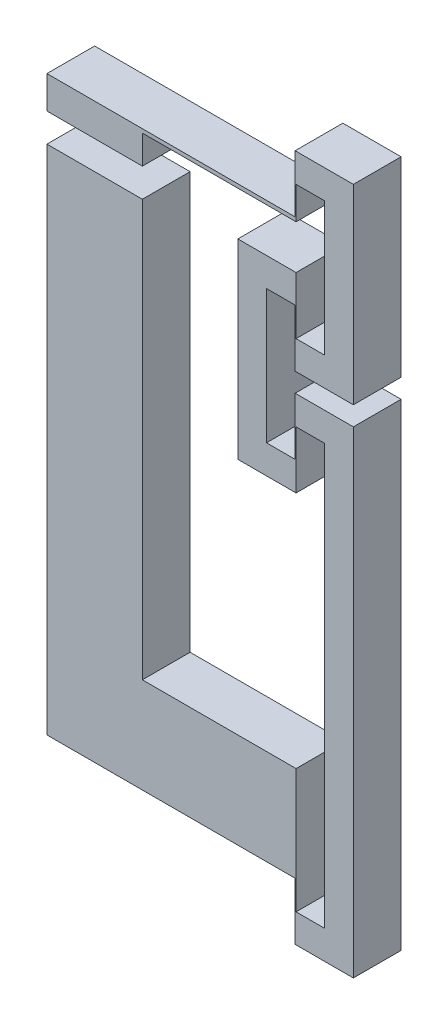
SolidWorks part; units mm, degrees
ref_plane "Front Plane" through (0, 0, 0) normal (0, 0, 1) x (1, 0, 0)
ref_plane "Top Plane" through (0, 0, 0) normal (0, 1, 0) x (1, 0, 0)
ref_plane "Right Plane" through (0, 0, 0) normal (1, 0, 0) x (0, 0, -1)
sketch "Sketch1" plane through (0, 0, 0) normal (0, 0, 1) x (1, 0, 0)
  line L0 (0, 0) -> (0, 53.6)
  line L4 (10, 10) -> (10, 53.6)
  line L5 (10, 53.6) -> (0, 53.6)
  line L6 (0, 56.6) -> (0, 60)
  line L7 (0, 60) -> (26, 60)
  line L8 (26.1, 60) -> (26.1, 59.6)
  line L9 (26.1, 59.6) -> (10, 59.6)
  line L10 (10, 59.6) -> (10, 56.6)
  line L11 (10, 56.6) -> (0, 56.6)
  line L12 (10, 10) -> (26.1, 10)
  line L20 (29.1, -3) -> (29.1, 41)
  line L24 (32.1, 44) -> (32.1, -6)
  line L32 (20, 35) -> (20, 55)
  line L33 (20, 55) -> (26.1, 55)
  line L36 (23, 52) -> (23, 38)
  line L41 (29.1, 63) -> (26.1, 63)
  line L44 (32.1, 66) -> (32.1, 46)
  line L47 (26.1, 60) -> (26.1, 63)
  line L48 (26, 60) -> (26, 66)
  line L49 (26, 66) -> (32.1, 66)
  line L55 (26.1, 55) -> (26.1, 52)
  line L78 (26.1, 49) -> (29.1, 49)
  line L82 (23, 52) -> (26, 52)
  line L83 (26.1, 52) -> (26.1, 49)
  line L84 (32.1, 46) -> (26, 46)
  line L85 (26, 46) -> (26, 52)
  line L86 (20, 35) -> (26.1, 35)
  line L87 (26.1, 35) -> (26.1, 36)
  line L88 (26, 38) -> (23, 38)
  line L89 (32.1, 44) -> (26, 44)
  line L91 (26.1, 41) -> (29.1, 41)
  line L92 (26.1, 36) -> (26.1, 41)
  line L97 (32.1, -6) -> (26, -6)
  line L98 (26, -6) -> (26, -3)
  line L100 (26, -3) -> (26, 0)
  line L101 (29.1, -3) -> (26.1, -3)
  line L105 (0, 0) -> (26, 0)
  line L108 (29.1, 63) -> (29.1, 49)
  line L109 (26, 44) -> (26, 38)
  line L110 (26.1, 10) -> (26.1, -3)
  dimension "D3" = 3
  dimension "D4" = 0.1
  dimension "D5" = 3
  dimension "D6" = 3
  dimension "D7" = 0.1
  dimension "D12" = 0.4
  dimension "D13" = 26
  dimension "D15" = 0.4
  dimension "D10" = 43.6
  dimension "D11" = 50
  dimension "D16" = 3
  dimension "D14" = 3
  dimension "D17" = 3
  dimension "D19" = 3
  dimension "D21" = 10
  dimension "D24" = 26
  dimension "D25" = 3.4
  dimension "D22" = 10
  dimension "D18" = 3
  dimension "D26" = 20
  dimension "D27" = 3
  dimension "D28" = 3
  dimension "D29" = 3
  dimension "D30" = 3
  dimension "D31" = 20
  dimension "D9" = 3
  dimension "D32" = 3
  dimension "D33" = 3
  dimension "D34" = 3
  dimension "D20" = 3
  dimension "D8" = 0.1
  dimension "D23" = 0.1
extrude "Boss-Extrude1" add sketch "Sketch1" along normal blind 5
equation "\"A.L\"= 0.05m"
equation "\"A.h\"= 0.003m"
equation "\"A.d\"= 0.003m"
equation "\"A.delta\"= 45.0001"
equation "\"A.w\"= 0.02m"
equation "\"A.v\"= 0.03m"
equation "\"B.L\"= 0.02m"
equation "\"B.h\"= 0.003m"
equation "\"C.h\"= 0.0004m"
equation "\"C.d\"= 0.003m"
equation "\"C.L\"= 0.016m"
equation "\"C.wmax\"= 0.003m"
equation "\"a_h\"= 0.0001m"
equation "\"a_d\"= 0.003m"
equation "\"a_L\"= 0.003m"
equation "\"b_h\"= 0.0001m"
equation "\"b_d\"= 0.003m"
equation "\"b_L\"= 0.003m"
equation "\"c_h\"= 0.0001m"
equation "\"c_d\"= 0.003m"
equation "\"c_L\"= 0.003m"
equation "\"S.h\"= 0.01m"
equation "\"S.L\"= 0.0468m"
equation "\"D4@Sketch1\"=\"c_h\""
equation "\"D5@Sketch1\"=\"c_L\""
equation "\"d_h\"= 0.0001m"
equation "\"d_L\"= 0.003m"
equation "\"d_d\"= 0.003m"
equation "\"D6@Sketch1\"=\"b_L\""
equation "\"D7@Sketch1\"=\"b_h\""
equation "\"D12@Sketch1\"=\"C.h\""
equation "\"D13@Sketch1\"=\"C.L\"+\"S.h\""
equation "\"D15@Sketch1\"=\"C.h\""
equation "\"A.t\"= 0.003m"
equation "\"A.s\"= 0.003m"
equation "\"D11@Sketch1\"=\"A.L\""
equation "\"D16@Sketch1\"=\"A.s\""
equation "\"D17@Sketch1\"=\"A.s\""
equation "\"D19@Sketch1\"=\"A.t\""
equation "\"D21@Sketch1\"=\"S.h\""
equation "\"D24@Sketch1\"=\"C.L\"+\"S.h\""
equation "\"D25@Sketch1\"=\"C.h\"+\"C.wmax\""
equation "\"D22@Sketch1\"=\"S.h\""
equation "\"D18@Sketch1\"=\"A.t\""
equation "\"B.t\"= 0.003m"
equation "\"B.s\"= 0.003m"
equation "\"D26@Sketch1\"=\"B.L\""
equation "\"D27@Sketch1\"=\"B.s\""
equation "\"D28@Sketch1\"=\"B.s\""
equation "\"D29@Sketch1\"=\"B.t\""
equation "\"D30@Sketch1\"=\"B.t\""
equation "\"D14@Sketch1\"=\"A.h\""
equation "\"D.L\"= 0.02m"
equation "\"D.h\"= 0.003m"
equation "\"D.s\"= 0.003m"
equation "\"D.t\"= 0.003m"
equation "\"D31@Sketch1\"=\"D.L\""
equation "\"D3@Sketch1\"=\"D.h\""
equation "\"D9@Sketch1\"=\"D.t\""
equation "\"D33@Sketch1\"=\"a_L\""
equation "\"D34@Sketch1\"=\"D.s\""
equation "\"D32@Sketch1\"=\"D.t\""
equation "\"D20@Sketch1\"=\"d_L\""
equation "\"D10@Sketch1\"=\"S.L\"-\"C.wmax\"-\"C.h\"/2"
equation "\"D8@Sketch1\"=\"d_h\""
equation "\"D23@Sketch1\"=\"d_h\""
